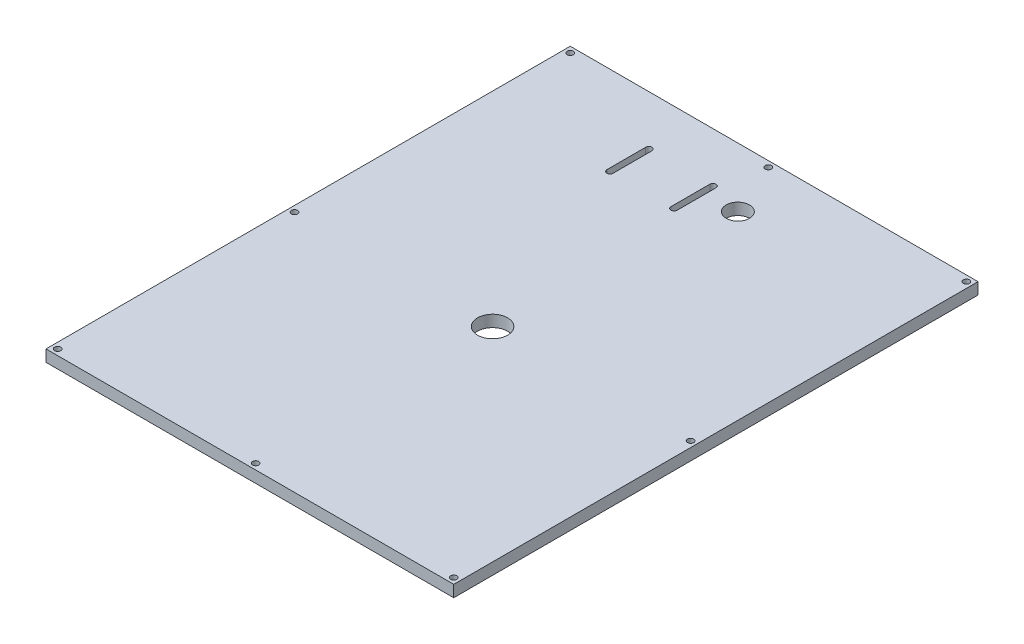
SolidWorks part; units mm, degrees
ref_plane "Front Plane" through (0, 0, 0) normal (0, 0, 1) x (1, 0, 0)
ref_plane "Top Plane" through (0, 0, 0) normal (0, 1, 0) x (1, 0, 0)
ref_plane "Right Plane" through (0, 0, 0) normal (1, 0, 0) x (0, 0, -1)
sketch "Sketch1" plane through (0, 0, 0) normal (0, 1, 0) x (1, 0, 0)
  line L0 (-75, 125) -> (75, 125)
  line L1 (-75, 125) -> (-75, -125)
  line L2 (-75, -125) -> (75, -125)
  line L3 (75, 125) -> (75, -125)
  line L4 (-75, 125) -> (75, -125) construction
  line L5 (-75, -125) -> (75, 125) construction
  circle A0 centre (-9.8995, 9.8995) radius 1.75
  circle A1 centre (9.8995, 9.8995) radius 1.75
  circle A2 centre (-9.8995, -9.8995) radius 1.75
  circle A3 centre (9.8995, -9.8995) radius 1.75
  point P0 (0, 0)
  dimension "D1" = 250
  dimension "D2" = 150
extrude "Boss-Extrude1" add sketch "Sketch1" along normal blind 6
sketch "Sketch2" plane through (0, 6, 0) normal (0, 1, 0) x (1, 0, 0)
  circle A0 centre (0, 0) radius 11.25
  dimension "D1" = 22.5
extrude "Cut-Extrude1" cut sketch "Sketch2" against normal blind 6
hole_wizard "CSK for M3 Flat Head Machine Screw1" positions "Sketch3" profile "Sketch4" countersink size "M3" standard "ANSI Metric" end condition through all
sketch "Sketch3" plane through (0, 6, 0) normal (0, 1, 0) x (1, 0, 0)
  point P0 (-9.8995, 9.8995)
  point P3 (9.8995, 9.8995)
  point P7 (-9.8995, -9.8995)
  point P10 (9.8995, -9.8995)
sketch "Sketch4" plane through (-9.8995, 6, -9.8995) normal (1, 0, 0) x (0, 0, 1)
  line L0 (0, 0) -> (0, 6)
  line L1 (0, 6) -> (1.7, 6)
  line L2 (1.7, 6) -> (1.7, 1.45)
  line L3 (1.7, 1.45) -> (3.15, 0)
  line L5 (3.15, 0) -> (0, 0)
  line L6 (-1.7, 1.45) -> (-3.15, 0) construction
  line L11 (0, -6.35) -> (0, 107.95) construction
  dimension "Thru Hole Dia." = 3.4
  dimension "Thru Hole Depth" = 6
  dimension "Near C'Sink Dia." = 6.3
  dimension "Near C'Sink Angle" = 90
sketch "Sketch5" plane through (0, 6, 0) normal (0, 1, 0) x (1, 0, 0)
  line L1 (-75, 125) -> (75, 125)
  line L2 (-75, 125) -> (-75, 145)
  line L3 (-75, 145) -> (75, 145)
  line L4 (75, 125) -> (75, 145)
  dimension "D1" = 20
extrude "Boss-Extrude2" add sketch "Sketch5" against normal up to surface (6 mm away) up to face at (0, 0, 11.25)
sketch "Sketch6" plane through (0, 6, 0) normal (0, 1, 0) x (1, 0, 0)
  line L0 (-38.9193, 114.3873) -> (-38.9193, 109.3873) construction
  line L1 (-38.9193, 114.3873) -> (-38.9193, 119.3873) construction
  line L2 (-38.9193, 119.3873) -> (-38.9193, 109.3873) construction
  line L3 (-37.3193, 119.3873) -> (-37.3193, 109.3873)
  line L4 (-40.5193, 119.3873) -> (-40.5193, 109.3873)
  line L5 (-22.4193, 132.3873) -> (-22.4193, 151.7575) construction
  line L6 (-2.9193, 132.3873) -> (-41.9193, 132.3873) construction
  line L7 (-5.9193, 119.3873) -> (-5.9193, 109.3873) construction
  line L8 (-7.5193, 119.3873) -> (-7.5193, 109.3873)
  line L9 (-4.3193, 119.3873) -> (-4.3193, 109.3873)
  line L10 (-5.9193, 114.3873) -> (-5.9193, 119.3873) construction
  line L11 (-5.9193, 114.3873) -> (-5.9193, 109.3873) construction
  arc A0 (-37.3193, 119.3873) -> (-40.5193, 119.3873) centre (-38.9193, 119.3873) ccw
  arc A1 (-40.5193, 109.3873) -> (-37.3193, 109.3873) centre (-38.9193, 109.3873) ccw
  arc A2 (-7.5193, 119.3873) -> (-4.3193, 119.3873) centre (-5.9193, 119.3873) cw
  arc A3 (-4.3193, 109.3873) -> (-7.5193, 109.3873) centre (-5.9193, 109.3873) cw
  point P4 (-38.9193, 114.3873)
  point P15 (-5.9193, 114.3873)
  dimension "D3" = 1.6
  dimension "D1" = 5
  dimension "D2" = 5
extrude "Cut-Extrude2" cut sketch "Sketch6" against normal blind 22
sketch "Sketch7" plane through (0, 6, 0) normal (0, 1, 0) x (-1, 0, 0)
  line L0 (4.3193, -114.3873) -> (-11.9275, -114.3873) construction
  line L1 (4.3193, -109.3873) -> (4.3193, -119.3873) construction
  circle A0 centre (-11.9275, -114.3873) radius 6
  dimension "D1" = 12
extrude "Cut-Extrude3" cut sketch "Sketch7" against normal blind 16
sketch "Sketch8" plane through (0, 6, 0) normal (0, 1, 0) x (1, 0, 0)
  line L0 (75, -125) -> (75, 145) construction
  line L1 (-75, 145) -> (-105, 145)
  line L2 (-75, 145) -> (-75, -125)
  line L3 (-75, -125) -> (-105, -125)
  line L4 (-105, 145) -> (-105, -125)
  line L5 (75, 145) -> (105, 145)
  line L6 (75, 145) -> (75, -125)
  line L7 (75, -125) -> (105, -125)
  line L8 (105, 145) -> (105, -125)
  line L9 (-75, -125) -> (75, -125) construction
  dimension "D1" = 30
  dimension "D2" = 30
extrude "Boss-Extrude3" add sketch "Sketch8" against normal up to surface (6 mm away) up to face at (11.9275, 0, -108.3873)
sketch "Sketch9" plane through (0, 6, 0) normal (0, 1, 0) x (1, 0, 0)
  line L0 (-102, -122) -> (102, -122) construction
  line L1 (102, -122) -> (102, 142) construction
  line L2 (102, 142) -> (-102, 142) construction
  line L3 (-102, 142) -> (-102, -122) construction
  line L4 (-105, -125) -> (105, -125)
  line L5 (105, -125) -> (105, 145)
  line L6 (105, 145) -> (-105, 145)
  line L7 (-105, 145) -> (-105, -125)
  line L8 (-105, -125) -> (105, -125) construction
  line L9 (105, -125) -> (105, 145) construction
  line L10 (105, 145) -> (-105, 145) construction
  line L11 (-105, 145) -> (-105, -125) construction
  circle A0 centre (-102, 142) radius 1.6
  circle A1 centre (0, 142) radius 1.6
  circle A2 centre (102, 142) radius 1.6
  circle A3 centre (-102, 0) radius 1.6
  circle A4 centre (102, 0) radius 1.6
  circle A5 centre (-102, -122) radius 1.6
  circle A6 centre (102, -122) radius 1.6
  circle A7 centre (0, -122) radius 1.6
  dimension "D3" = 3.2
  dimension "D1" = 0
  dimension "D2" = 3
extrude "Cut-Extrude4" cut sketch "Sketch9" against normal blind 10
sketch "Sketch10" plane through (0, 6, 0) normal (0, 1, 0) x (1, 0, 0)
  line L1 (-15.5, 15.5) -> (15.5, 15.5) construction
  line L2 (-15.5, 15.5) -> (-15.5, -15.5) construction
  line L3 (-15.5, -15.5) -> (15.5, -15.5) construction
  line L4 (15.5, 15.5) -> (15.5, -15.5) construction
  line L5 (-15.5, 15.5) -> (15.5, -15.5) construction
  line L6 (-15.5, -15.5) -> (15.5, 15.5) construction
  circle A0 centre (-15.5, 15.5) radius 1.6
  circle A1 centre (-15.5, -15.5) radius 1.6
  circle A2 centre (15.5, 15.5) radius 1.6
  circle A3 centre (15.5, -15.5) radius 1.6
  point P0 (0, 0)
  dimension "D3" = 3.2
  dimension "D1" = 31
  dimension "D2" = 31
extrude "Cut-Extrude5" cut sketch "Sketch10" against normal blind 10
hole_wizard "CSK for M3.5 Flat Head Machine Screw1" positions "Sketch11" profile "Sketch12" countersink size "M3.5" standard "ANSI Metric"
sketch "Sketch11" plane through (0, 6, 0) normal (0, 1, 0) x (1, 0, 0)
  point P0 (-15.5, 15.5)
  point P3 (-15.5, -15.5)
  point P6 (15.5, -15.5)
  point P9 (15.5, 15.5)
sketch "Sketch12" plane through (-15.5, 6, -15.5) normal (1, 0, 0) x (0, 0, 1)
  line L0 (0, 0) -> (0, 7.1116)
  line L1 (0, 7.1116) -> (1.85, 6)
  line L2 (1.85, 6) -> (1.85, 2.25)
  line L3 (1.85, 2.25) -> (4.1, 0)
  line L5 (4.1, 0) -> (0, 0)
  line L6 (-1.85, 2.25) -> (-4.1, 0) construction
  line L10 (0, 7.1116) -> (-1.85, 6) construction
  line L11 (0, -6.35) -> (0, 107.95) construction
  dimension "Hole Dia." = 3.7
  dimension "Hole Depth" = 6
  dimension "Near C'Sink Dia." = 8.2
  dimension "Near C'Sink Angle" = 90
  dimension "Drill Angle" = 118
sketch "Sketch13" plane through (0, 6, 0) normal (0, 1, 0) x (1, 0, 0)
  line L1 (-41.4329, 95.6479) -> (-31.4329, 95.6479)
  line L2 (-41.4329, 95.6479) -> (-41.4329, -87)
  line L3 (-41.4329, -87) -> (-31.4329, -87)
  line L4 (-31.4329, 95.6479) -> (-31.4329, -87)
  line L5 (-25.9329, 95.6479) -> (-15.9329, 95.6479)
  line L6 (-25.9329, 95.6479) -> (-25.9329, -87)
  line L7 (-25.9329, -87) -> (-15.9329, -87)
  line L8 (-15.9329, 95.6479) -> (-15.9329, -87)
  line L9 (15.9329, 95.6479) -> (25.9329, 95.6479)
  line L10 (15.9329, 95.6479) -> (15.9329, -87)
  line L11 (15.9329, -87) -> (25.9329, -87)
  line L12 (25.9329, 95.6479) -> (25.9329, -87)
  line L13 (31.4329, 95.6479) -> (41.4329, 95.6479)
  line L14 (31.4329, 95.6479) -> (31.4329, -87)
  line L15 (31.4329, -87) -> (41.4329, -87)
  line L16 (41.4329, 95.6479) -> (41.4329, -87)
sketch "Sketch14" plane through (0, 0, 0) normal (0, -1, 0) x (1, 0, 0)
  line L1 (24.5625, 29.0497) -> (-24.5625, 29.0497)
  line L2 (24.5625, 29.0497) -> (24.5625, -29.0497)
  line L3 (24.5625, -29.0497) -> (-24.5625, -29.0497)
  line L4 (-24.5625, 29.0497) -> (-24.5625, -29.0497)
  line L5 (24.5625, 29.0497) -> (-24.5625, -29.0497) construction
  line L6 (24.5625, -29.0497) -> (-24.5625, 29.0497) construction
  point P0 (0, 0)
extrude "Boss-Extrude4" add sketch "Sketch14" against normal up to surface (6 mm away) up to face at (-15.5, 6, -11.4)
sketch "Sketch15" plane through (0, 0, 0) normal (0, -1, 0) x (1, 0, 0)
  circle A0 centre (0, 0) radius 7.75
  dimension "D1" = 15.5
extrude "Cut-Extrude6" cut sketch "Sketch15" against normal blind 10
sketch "Sketch16" plane through (0, 0, 0) normal (0, -1, 0) x (1, 0, 0)
  line L4 (-105, -145) -> (105, -145)
  line L5 (105, -145) -> (105, 125)
  line L6 (105, 125) -> (-105, 125)
  line L7 (-105, 125) -> (-105, -145)
  line L8 (-105, -145) -> (105, -145)
  line L9 (105, -145) -> (105, 125)
  line L10 (105, 125) -> (-105, 125)
  line L11 (-105, 125) -> (-105, -145)
  circle A0 centre (0, 0) radius 7.75
  dimension "D1" = 0
sketch "Sketch17" plane through (0, 0, 0) normal (0, -1, 0) x (1, 0, 0)
  line L0 (-38.9193, -119.3873) -> (-38.9193, -99.3873) construction
  line L1 (-40.5193, -119.3873) -> (-40.5193, -99.3873)
  line L2 (-37.3193, -119.3873) -> (-37.3193, -99.3873)
  line L3 (-40.5193, -119.3873) -> (-40.5193, -109.3873) construction
  line L4 (-5.9193, -119.3873) -> (-5.9193, -99.3873) construction
  line L5 (-7.5193, -119.3873) -> (-7.5193, -99.3873)
  line L6 (-4.3193, -119.3873) -> (-4.3193, -99.3873)
  arc A0 (-40.5193, -119.3873) -> (-37.3193, -119.3873) centre (-38.9193, -119.3873) ccw
  arc A1 (-37.3193, -99.3873) -> (-40.5193, -99.3873) centre (-38.9193, -99.3873) ccw
  arc A2 (-7.5193, -119.3873) -> (-4.3193, -119.3873) centre (-5.9193, -119.3873) ccw
  arc A3 (-4.3193, -99.3873) -> (-7.5193, -99.3873) centre (-5.9193, -99.3873) ccw
  point P3 (-38.9193, -109.3873)
  point P13 (-5.9193, -109.3873)
  dimension "D2" = 1.6
  dimension "D1" = 20
  dimension "D3" = 20
extrude "Cut-Extrude7" cut sketch "Sketch17" against normal blind 10
